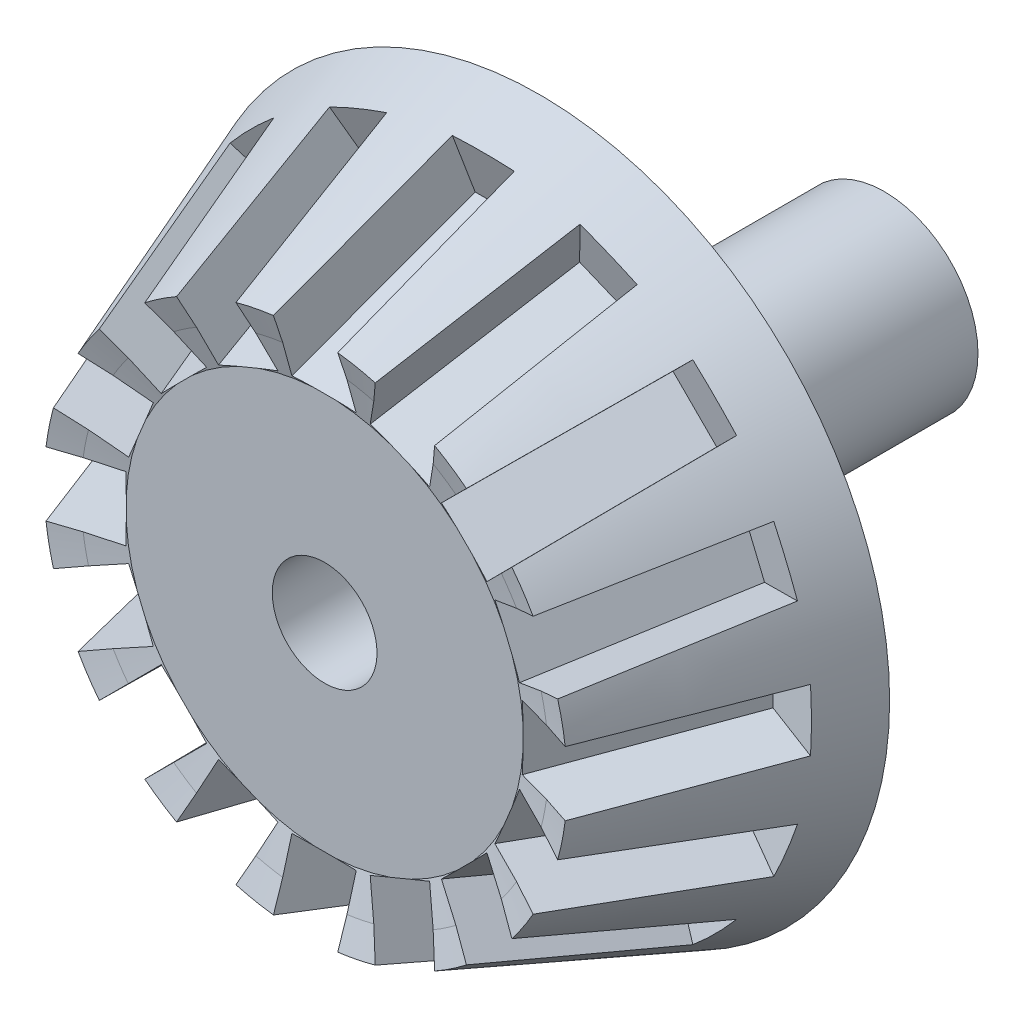
SolidWorks part; units mm, degrees
ref_plane "Front Plane" through (0, 0, 0) normal (0, 0, 1) x (1, 0, 0)
ref_plane "Top Plane" through (0, 0, 0) normal (0, 1, 0) x (1, 0, 0)
ref_plane "Right Plane" through (0, 0, 0) normal (1, 0, 0) x (0, 0, -1)
sketch "Sketch1" plane through (0, 0, 0) normal (1, 0, 0) x (0, 0, -1)
  line L0 (0, 0) -> (48.6951, 0) construction
  line L1 (0, 0) -> (36.3475, 10.1484) construction
  line L2 (0, 0) -> (36.0149, 12.0015) construction
  line L3 (0, 0) -> (35.7458, 13.5001) construction
  line L11 (35.7458, 13.5001) -> (26.7163, 10.0899)
  line L18 (27.4513, 0) -> (36.3475, 0)
  line L19 (35.7458, 13.5001) -> (36.3475, 10.1484)
  line L21 (26.7163, 10.0899) -> (27.0724, 9.0215)
  line L22 (27.0724, 9.0215) -> (27.4513, 7.6645)
  line L23 (27.4513, 7.6645) -> (27.4513, 0)
  line L26 (36.3475, 10.1484) -> (36.3475, 0)
  dimension "D1" = 15.6
  dimension "D2" = 18.43
  dimension "D3" = 20.69
  dimension "D4" = 9.652
  dimension "D6" = 12.0015
  dimension "D7" = 13.5001
revolve "Revolve1" add sketch "Sketch1" angle 360 about L0
ref_plane "Plane7" through (0, 0, 0) normal (0, 0.9355, 0.3533) x (1, 0, 0)
sketch "Sketch2" plane through (0, 0, 0) normal (0, 0.9355, 0.3533) x (1, 0, 0)
  line L0 (0, 40.6052) -> (0, 16.5207) construction
  line L1 (0, 0) -> (0, 45.5546) construction
  line L2 (1.2446, 27.7092) -> (1.1938, 35.867)
  line L3 (0, 27.7092) -> (1.2446, 27.7092)
  line L5 (1.1938, 35.867) -> (0, 35.867)
  line L9 (-1.1938, 35.867) -> (0, 35.867)
  line L10 (0, 27.7092) -> (-1.2446, 27.7092)
  line L11 (-1.2446, 27.7092) -> (-1.1938, 35.867)
  dimension "D1" = 2.3876
  dimension "D2" = 2.4892
extrude "Cut-Extrude2" cut sketch "Sketch2" against normal blind 2.54 contours L5 L9 L11 L10 L3 L2 body kept at (0, 13.5001, -35.7458)
pattern_circular "CirPattern2" count 16 over 360 about axis through (0, 0, -27.0724) along (0, 0, 1) of "Revolve1", "Cut-Extrude2"
extrude "Cut-Extrude3" cut sketch "Sketch2<4>" against normal blind 2.54
sketch "Sketch2<4>" plane through (0, 0, 0) normal (0, 0.9355, 0.3533) x (1, 0, 0) same geometry as "Sketch2"
sketch "Sketch3" plane through (0, 0, -36.3475) normal (0, 0, -1) x (-1, 0, 0)
  circle A0 centre (0, 0) radius 3.6068
  circle A1 centre (0, 0) radius 2.0193
  dimension "D1" = 7.2136
  dimension "D2" = 4.0386
extrude "Boss-Extrude1" add sketch "Sketch3" along normal blind 12.7
sketch "Sketch4" plane through (0, 0, -36.3475) normal (0, 0, -1) x (-1, 0, 0)
  circle A0 centre (0, 0) radius 2.0193
  dimension "D1" = 4.0386
extrude "Cut-Extrude4" cut sketch "Sketch4" against normal through all both and the other way through all
